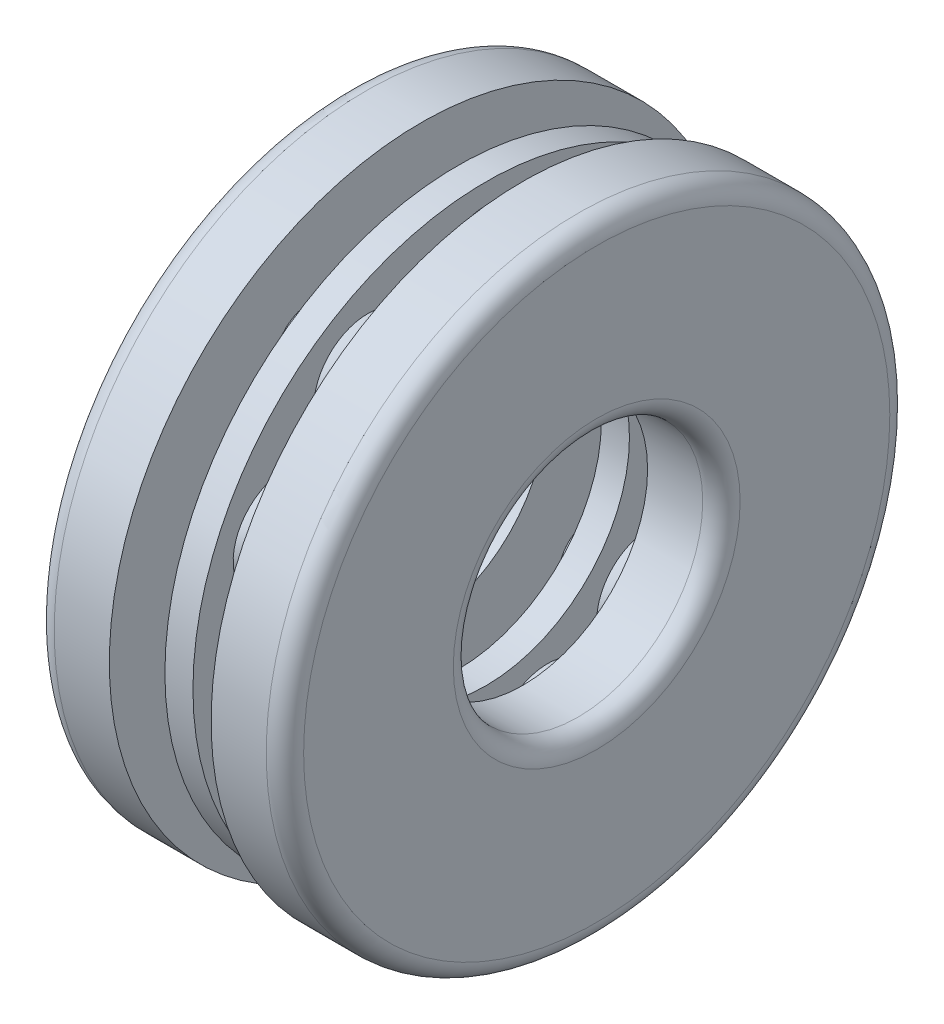
SolidWorks part; units mm, degrees
note: '?' marks a value the reader was unsure of.
ref_plane "Plane1" through (0, 0, 0) normal (0, 0, 1) x (1, 0, 0)
ref_plane "Plane2" through (0, 0, 0) normal (0, 1, 0) x (1, 0, 0)
ref_plane "Plane3" through (0, 0, 0) normal (1, 0, 0) x (0, 0, -1)
sketch "Clipboard" plane through (0, 0, 0) normal (0, 0, 1) x (1, 0, 0)
  line L0 (-10, 0) -> (10, 0) construction
  line L1 (0, 0) -> (21.7876, -5.0301)
  line L2 (0, 0) -> (3.4995, -0.0611)
  line L3 (0, 0) -> (21.7876, -5.0301)
  line L4 (0, 0) -> (-22.3471, -0.7804)
  dimension "BallCLRad" = 3.5
sketch "InnRacSke" plane through (0, 0, 0) normal (0, 0, 1) x (1, 0, 0)
  line L0 (-0.816, 3.1841) -> (-0.816, 2)
  line L1 (-0.816, 2) -> (-1.7, 2)
  line L2 (-2, 2.3) -> (-2, 4.7)
  line L3 (-1.7, 5) -> (-0.816, 5)
  line L4 (-0.816, 5) -> (-0.816, 3.8159)
  line L5 (-34.925, 0) -> (34.925, 0) construction
  line L6 (0, 0) -> (0, 25.4) construction
  arc A0 (-1.7, 2) -> (-2, 2.3) centre (-1.7, 2.3) cw
  arc A1 (-2, 4.7) -> (-1.7, 5) centre (-1.7, 4.7) cw
  arc A2 (-0.816, 3.8159) -> (-0.816, 3.1841) centre (0, 3.5) ccw
  dimension "BallCLRad" = 3.5
revolve "Race" add sketch "InnRacSke" angle 360 about L5
ref_axis "Axis1" through (-50, 0, 0) along (1, 0, 0)?
sketch "BalDetSke" plane through (0, 0, 0) normal (0, 0, 1) x (1, 0, 0)
  line L0 (-0.9, 3.5) -> (0.9, 3.5)
  line L1 (-14.5732, 3.5) -> (14.5732, 3.5) construction
  arc A0 (0.9, 3.5) -> (-0.9, 3.5) centre (0, 3.5) cw
  dimension "BallCLRad" = 3.5
  dimension "Ball_diameter" = 1.8
revolve "BallDetailed" add sketch "BalDetSke" angle 360 about L1
sketch "BalSimSke" plane through (0, 0, 0) normal (0, 0, 1) x (1, 0, 0)
  line L0 (-25.4, 0) -> (25.4, 0) construction
  circle A0 centre (0, 3.5) radius 0.9
  dimension "BallCLRad" = 3.5
  dimension "Ball_diameter" = 1.8
revolve "BallsSimplified" [suppressed] add sketch "BalSimSke" angle 360 about L0
mirror "Mirror1" about plane through (0, 0, 0) normal (1, 0, 0) of "Race"
pattern_circular "BallsDetailed" count 11 over 360 about axis through (0, 0, 0) along (1, 0, 0) of "BallDetailed"
sketch "CagSpiSke" plane through (0, 0, 0) normal (0, 0, 1) x (1, 0, 0)
  line L0 (0.225, 2.3) -> (0.225, 4.7)
  line L1 (0.225, 4.7) -> (-0.225, 4.7)
  line L2 (-0.225, 4.7) -> (-0.225, 2.3)
  line L3 (-0.225, 2.3) -> (0.225, 2.3)
  line L4 (-34.925, 0) -> (34.925, 0) construction
  line L5 (0, 0) -> (0, 50.8) construction
  dimension "ID" = 4.6
  dimension "OD" = 9.4
revolve "CageSpine" add sketch "CagSpiSke" angle 360 about L4
equation "\"BallCLRad@Clipboard\" =  ( \"OD@InnRacSke\" + \"ID@InnRacSke\" )  / 4"
equation "\"BallCLRad@BalSimSke\" = \"BallCLRad@Clipboard\""
equation "\"BallCLRad@BalDetSke\" = \"BallCLRad@Clipboard\""
equation "\"BallCLRad@InnRacSke\" = \"BallCLRad@Clipboard\""
equation "\"Ball_diameter@InnRacSke\" = \"Ball_diameter@BalDetSke\" - 0.05"
equation "\"Ball_diameter@BalSimSke\" = \"Ball_diameter@BalDetSke\""
equation "\"Max_count@Clipboard\"= int ( 3.14159265 / atn ( ( \"Ball_diameter@BalDetSke\" / 2 ) / sqr ( \"BallCLRad@Clipboard\" * \"BallCLRad@Clipboard\" - ( \"Ball_diameter@BalDetSke\" / 2 ) * ( \"Ball_diameter@BalDetSke\" / 2 ) ) ) )"
equation "\"Max_count@Clipboard\"= ( ( sgn ( \"Max_count@Clipboard\" - \"Count@Clipboard\" ) - 1 ) * ( \"Max_count@Clipboard\" - \"Count@Clipboard\" ) ) / - 2 + \"Count@Clipboard\""
equation "\"Count@BallsDetailed\" = int( \"Show_count@Clipboard\" ) "
equation "\"Count@BallsDetailed\" = ((sgn( \"Count@BallsDetailed\" - \"Max_count@Clipboard\" )-1)*( \"Count@BallsDetailed\" - \"Max_count@Clipboard\" ))/-2+ \"Max_count@Clipboard\""
equation "\"Angle@CageSpine\" =  \"Angle@BallsDetailed\" * ( \"Count@BallsDetailed\" -1 + int( \"Count@BallsDetailed\" / \"Max_count@Clipboard\" ) )  + 0.001 -  int( \"Count@BallsDetailed\" / \"Max_count@Clipboard\" ) * 0.001"
equation "\"Thickness@CagSpiSke\" =  \"Ball_diameter@BalDetSke\" * 0.25"
equation "\"OD@CagSpiSke\" = ( \"OD@InnRacSke\" + ( \"BallCLRad@Clipboard\" * 2 + \"Ball_diameter@BalDetSke\" )) / 2"
equation "\"ID@CagSpiSke\" = ( \"ID@InnRacSke\" + ( \"BallCLRad@Clipboard\" * 2 - \"Ball_diameter@BalDetSke\" )) / 2"
